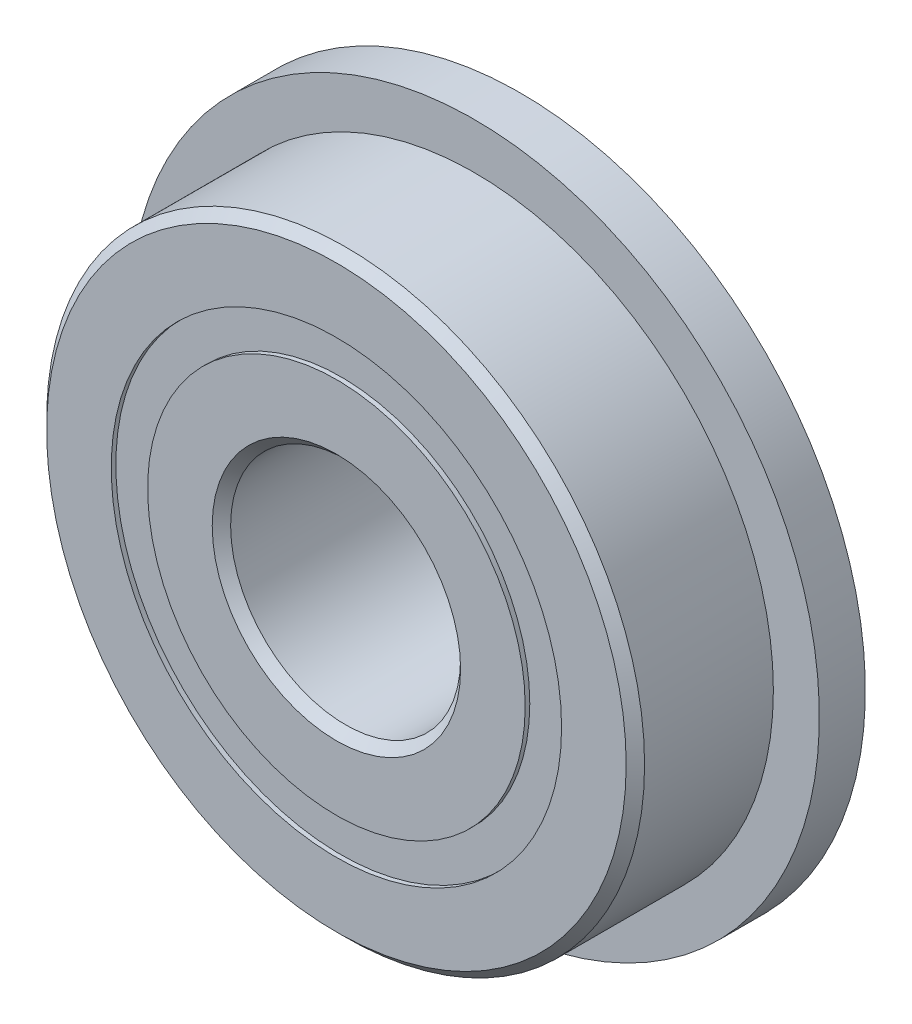
SolidWorks part; units mm, degrees
ref_plane "Front Plane" through (0, 0, 0) normal (0, 0, 1) x (1, 0, 0)
ref_plane "Top Plane" through (0, 0, 0) normal (0, 1, 0) x (1, 0, 0)
ref_plane "Right Plane" through (0, 0, 0) normal (1, 0, 0) x (0, 0, -1)
sketch "Sketch1" plane through (0, 0, 0) normal (1, 0, 0) x (0, 0, -1)
  line L0 (-2, 0) -> (2, 0) construction
  line L1 (0, 6.5) -> (0, -6.5) construction
  line L2 (1.8, 6.5) -> (-1.8, 6.5)
  line L3 (-1.8, 6.5) -> (-2, 6.3)
  line L4 (-2, 6.3) -> (-2, 4.8956)
  line L5 (-2, 4.8956) -> (-0.8889, 4.8956)
  line L6 (2, 4.8956) -> (0.8889, 4.8956)
  line L7 (2, 6.3) -> (2, 4.8956)
  line L8 (1.8, 6.5) -> (2, 6.3)
  line L9 (0, 6.5) -> (0, 4.5) construction
  line L10 (0, 4.5) -> (0, 2.5) construction
  arc A0 (-0.8889, 4.8956) -> (0.8889, 4.8956) centre (0, 4.5) cw
  point P14 (0, 2.5)
  dimension "Width" = 4
  dimension "OD" = 13
  dimension "D1" = 45
  dimension "D2" = 0.2
  dimension "Shaft Dia" = 5
  dimension "D3" = 1.7778
  dimension "D4" = 0.3956
revolve "Revolve1" add sketch "Sketch1" angle 360 about L0
sketch "Sketch3" plane through (0, 0, 0) normal (1, 0, 0) x (0, 0, -1)
  line L0 (-2, 4.1044) -> (-0.8889, 4.1044)
  line L1 (0, 6.5) -> (0, -6.5) construction
  line L2 (-2, 6.3) -> (-2, 4.8956) construction
  line L3 (-2, 4.1044) -> (-2, 2.7)
  line L4 (-1.8, 6.5) -> (-2, 6.3) construction
  line L5 (-2, 2.7) -> (-1.8, 2.5)
  line L6 (-1.8, 2.5) -> (1.8, 2.5)
  line L7 (1.8, 6.5) -> (1.8, -6.5) construction
  line L8 (1.8, 2.5) -> (2, 2.7)
  line L9 (2, -6.3) -> (2, 6.3) construction
  line L10 (2, 2.7) -> (2, 4.1044)
  line L11 (2, 4.1044) -> (0.8889, 4.1044)
  line L13 (1.8, 6.5) -> (2, 6.3) construction
  arc A0 (0.8889, 4.8956) -> (-0.8889, 4.8956) centre (0, 4.5) ccw construction
  arc A1 (0.8889, 4.1044) -> (-0.8889, 4.1044) centre (0, 4.5) cw
revolve "Revolve3" add sketch "Sketch3" angle 360 about L0
sketch "Sketch4" plane through (0, 0, 0) normal (1, 0, 0) x (0, 0, -1)
  line L0 (-0.9729, 4.5) -> (0.9729, 4.5)
  arc A2 (-0.9729, 4.5) -> (0.9729, 4.5) centre (0, 4.5) cw
  arc A3 (0.8889, 4.8956) -> (-0.8889, 4.8956) centre (0, 4.5) ccw construction
revolve "Revolve4" [suppressed] add sketch "Sketch4" angle 360 about L0
ref_axis "Axis1" through (0, 0, -2) along (0, 0, 1)
pattern_circular "CirPattern1" [suppressed] count 12 every 30 about axis through (0, 0, -2) along (0, 0, 1) of bodies 104
sketch "Sketch5" plane through (0, 0, 0) normal (1, 0, 0) x (0, 0, -1)
  line L0 (-2, 4.8956) -> (-0.8889, 4.8956) construction
  line L1 (-1.9, 4.8956) -> (-0.9729, 4.8956)
  line L2 (-1.9, 4.8956) -> (-1.9, 4.1044)
  line L3 (-1.9, 4.1044) -> (-0.9729, 4.1044)
  line L4 (-0.9729, 4.8956) -> (-0.9729, 4.1044)
  line L5 (-2, 4.1044) -> (-0.8889, 4.1044) construction
  line L6 (2, 4.8956) -> (0.8889, 4.8956) construction
  line L7 (1.9, 4.8956) -> (0.9729, 4.8956)
  line L8 (1.9, 4.8956) -> (1.9, 4.1044)
  line L9 (1.9, 4.1044) -> (0.9729, 4.1044)
  line L10 (0.9729, 4.8956) -> (0.9729, 4.1044)
  line L11 (2, 4.1044) -> (0.8889, 4.1044) construction
  line L12 (-1.8, 6.5) -> (-2, 6.3) construction
  point P18 (-1.9, 6.4)
revolve "Revolve5" add sketch "Sketch5" angle 360 about L0
sketch "Sketch6" plane through (0, 0, 0) normal (1, 0, 0) x (0, 0, -1)
  line L0 (2, 0) -> (-2, 0) construction
  line L1 (2, 4.8956) -> (1, 4.8956)
  line L2 (2, 4.8956) -> (2, 7.5)
  line L3 (2, 7.5) -> (1, 7.5)
  line L4 (1, 4.8956) -> (1, 7.5)
  dimension "Th" = 1
  dimension "Flange OD" = 15
revolve "Revolve6" add sketch "Sketch6" angle 360 about L0
equation "\"D2@Sketch1\" = \"Width@Sketch1\"*.05"
equation "\"D3@Sketch1\" = \"Width@Sketch1\"/2.25"
equation "\"D4@Sketch1\" = (((\"OD@Sketch1\"-\"Width@Sketch1\")/2)/3.25)/3.5"
equation "\"D2@CirPattern1\" = 360/\"Balls@CirPattern1\""
